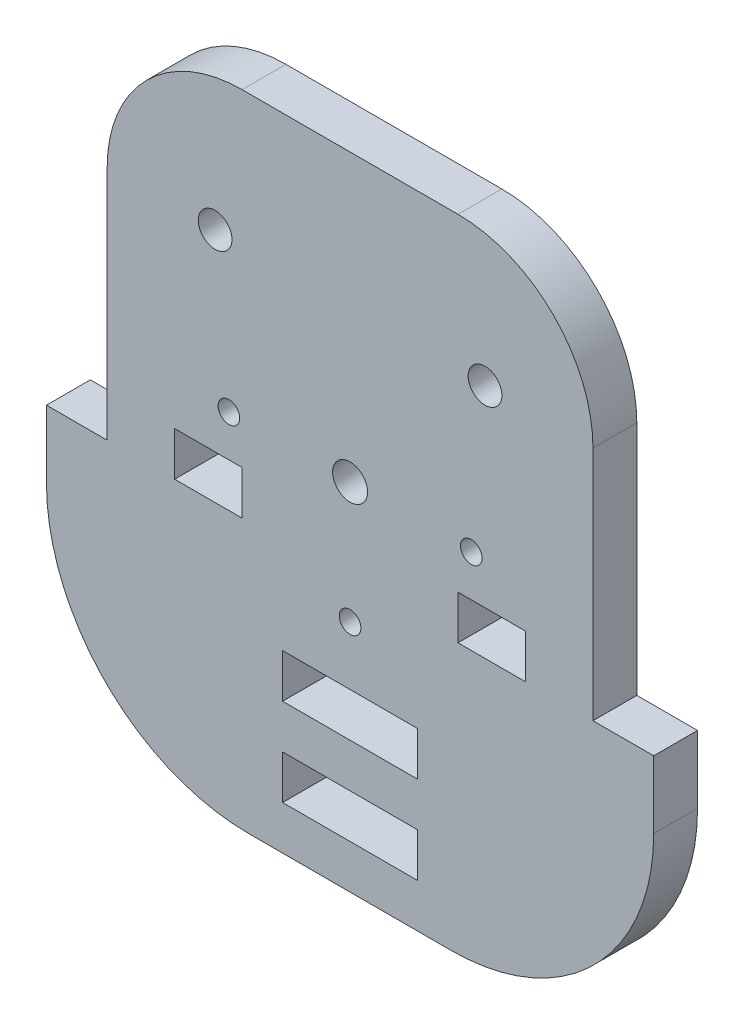
SolidWorks part; units mm, degrees
ref_plane "Front Plane" through (0, 0, 0) normal (0, 0, 1) x (1, 0, 0)
ref_plane "Top Plane" through (0, 0, 0) normal (0, 1, 0) x (1, 0, 0)
ref_plane "Right Plane" through (0, 0, 0) normal (1, 0, 0) x (0, 0, -1)
sketch "Sketch1" plane through (0, 0, 0) normal (0, 0, 1) x (1, 0, 0)
  line L1 (0, 0) -> (90, 0)
  line L2 (0, 0) -> (0, 40)
  line L3 (0, 40) -> (90, 40)
  line L4 (90, 0) -> (90, 40)
  line L5 (9, 95) -> (81, 95)
  line L6 (9, 95) -> (9, 40)
  line L7 (9, 40) -> (81, 40)
  line L8 (81, 95) -> (81, 40)
  dimension "D1" = 90
  dimension "D2" = 40
  dimension "D3" = 55
  dimension "D4" = 72
  dimension "D5" = 9
extrude "Boss-Extrude1" add sketch "Sketch1" along normal blind 6.5 contours L8 L5 L6 L3 | L1 L4 L3 L2 region at (45, 20, 0) region at (45, 67.5, 0)
fillet "Fillet1" radius 20 2 edges at (81, 95, 3.25) (9, 95, 3.25)
fillet "Fillet2" radius 30 2 edges at (90, 0, 3.25) (0, 0, 3.25)
sketch "Sketch2" plane through (0, 0, 6.5) normal (0, 0, 1) x (1, 0, 0)
  line L0 (9, 75) -> (9, 40) construction
  line L1 (45, 70.5998) -> (62.9605, 52.6393)
  line L2 (45, 70.5998) -> (27.0395, 52.6393)
  line L3 (27.0395, 52.6393) -> (45, 34.6788)
  line L4 (62.9605, 52.6393) -> (45, 34.6788)
  line L5 (45, 70.5998) -> (45, 34.6788) construction
  line L6 (27.0395, 52.6393) -> (62.9605, 52.6393) construction
  line L8 (0, 40) -> (9, 40) construction
  circle A0 centre (25, 75) radius 2.5
  circle A1 centre (65, 75) radius 2.5
  circle A2 centre (45, 52.6393) radius 2.5906
  circle A4 centre (62.9605, 52.6393) radius 1.6
  circle A5 centre (45, 34.6788) radius 1.6
  circle A6 centre (27.0395, 52.6393) radius 1.6
  dimension "D1" = 3.2
  dimension "D2" = 3.2
  dimension "D3" = 3.2
  dimension "D9" = 0
  dimension "D16" = 5
  dimension "D17" = 5
  dimension "D4" = 25.4
  dimension "D5" = 25.4
  dimension "D6" = 0
  dimension "D7" = 0
  dimension "D8" = 0
  dimension "D10" = 0
  dimension "D11" = 0
  dimension "D12" = 36
  dimension "D13" = 40
  dimension "D14" = 30
  dimension "D15" = 30
  dimension "D20" = 35
extrude "mount holes" cut sketch "Sketch2" against normal through all contours A0 | A1 | L2 A6 L3 | L3 A6 L2 | A2 | L1 A4 L4 | L4 A4 L1 | L3 A5 L4 | L4 A5 L3 region at (63.2806, 52.6393, 6.5) region at (62.0002, 52.6393, 6.5) region at (27.9998, 52.6393, 6.5) region at (26.7194, 52.6393, 6.5) region at (45, 34.3587, 6.5) region at (45, 35.6391, 6.5) region at (25, 75, 6.5) region at (65, 75, 6.5) region at (45, 52.6393, 6.5)
sketch "Sketch3" plane through (0, 0, 6.5) normal (0, 0, 1) x (1, 0, 0)
  line L1 (19, 40) -> (29, 40)
  line L2 (19, 40) -> (19, 46.5)
  line L3 (19, 46.5) -> (29, 46.5)
  line L4 (29, 40) -> (29, 46.5)
  line L5 (71, 40) -> (61, 40)
  line L6 (71, 40) -> (71, 46.5)
  line L7 (71, 46.5) -> (61, 46.5)
  line L8 (61, 40) -> (61, 46.5)
  dimension "D1" = 6.5
  dimension "D2" = 6.5
  dimension "D3" = 10
  dimension "D4" = 10
  dimension "D5" = 10
  dimension "D6" = 10
extrude "sidewheel cut" cut sketch "Sketch3" against normal up to next
sketch "Sketch4" plane through (0, 0, 6.5) normal (0, 0, 1) x (1, 0, 0)
  line L0 (30, 0) -> (60, 0) construction
  line L1 (35, 26) -> (55, 26)
  line L2 (35, 26) -> (35, 19.5)
  line L3 (35, 19.5) -> (55, 19.5)
  line L4 (55, 26) -> (55, 19.5)
  line L5 (35, 13) -> (55, 13)
  line L6 (35, 13) -> (35, 6.5)
  line L7 (35, 6.5) -> (55, 6.5)
  line L8 (55, 13) -> (55, 6.5)
  line L9 (45, 0) -> (45, 6.5) construction
  dimension "D1" = 6.5
  dimension "D2" = 6.5
  dimension "D3" = 6.5
  dimension "D4" = 6.5
  dimension "D5" = 20
extrude "crossbar cut" cut sketch "Sketch4" against normal through all
